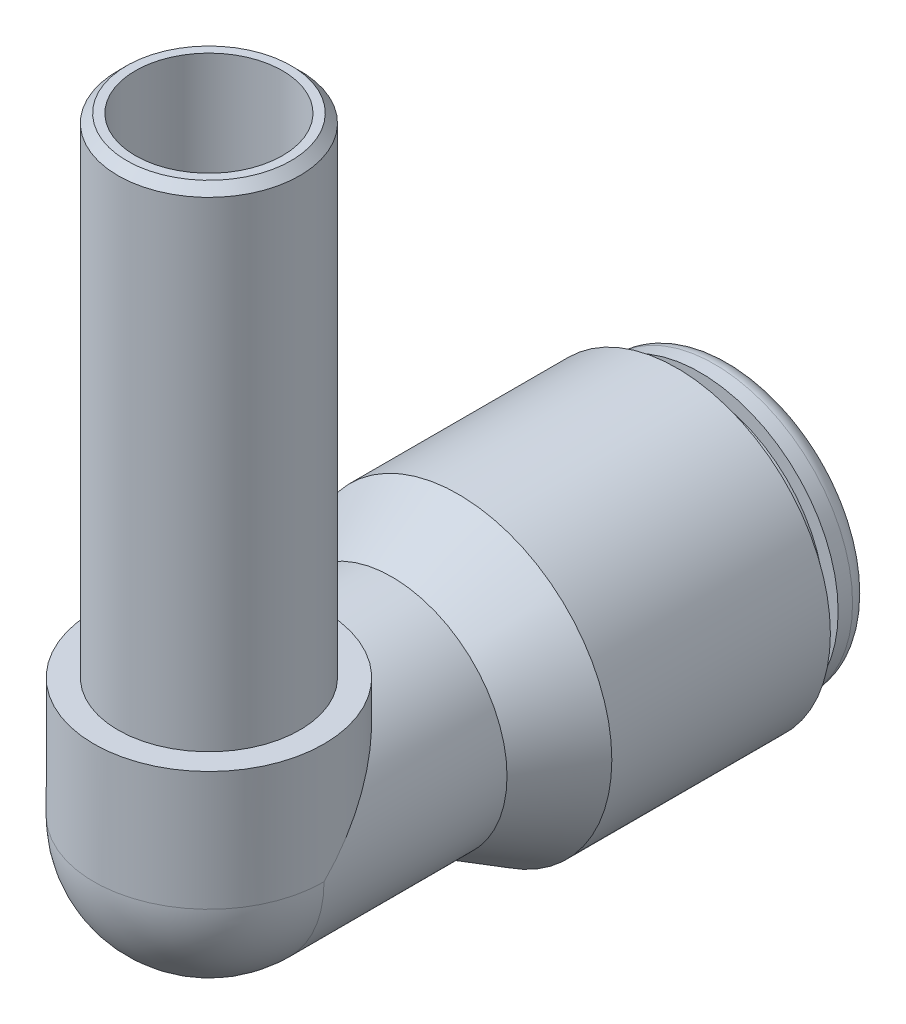
SolidWorks part; units mm, degrees
ref_plane "Front Plane" through (0, 0, 0) normal (0, 0, 1) x (1, 0, 0)
ref_plane "Top Plane" through (0, 0, 0) normal (0, 1, 0) x (1, 0, 0)
ref_plane "Right Plane" through (0, 0, 0) normal (1, 0, 0) x (0, 0, -1)
sketch "Sketch8" plane through (0, 0, 0) normal (1, 0, 0) x (0, 0, -1)
  line L0 (21.603, 6.075) -> (22.238, 6.075)
  line L1 (10.9728, 6.75) -> (20.587, 6.75)
  line L2 (0, 5.0625) -> (0, 4)
  line L3 (0, 4) -> (22.619, 4)
  line L4 (23, 5.313) -> (23, 4.381)
  line L5 (0, 6.75) -> (0, -16.25) construction
  line L6 (20.587, 6.75) -> (20.587, 5.4675)
  line L7 (20.587, 5.4675) -> (21.603, 5.4675)
  line L8 (21.603, 6.075) -> (21.603, 5.4675)
  line L9 (-6.75, -16.25) -> (6.75, -16.25) construction
  line L10 (0, 0) -> (23, 0) construction
  line L11 (23, -6.75) -> (0, -6.75) construction
  line L12 (22.619, 4) -> (23, 4.381)
  line L13 (0, 0) -> (0, 4) construction
  line L14 (0, 5.0625) -> (8.05, 5.0625)
  line L15 (8.05, 5.0625) -> (10.9728, 6.75)
  line L16 (0, -6.75) -> (0, 26.75) construction
  arc A0 (22.238, 6.075) -> (23, 5.313) centre (22.238, 5.313) cw
  point P1 (23, 4)
  point P20 (23, 6.075)
  point P24 (0, 5.25)
  point P26 (23, 6.75)
  point P27 (23, -6.75)
  point P28 (0, 8)
  dimension "D4" = 0.762
  dimension "tube od" = 8
  dimension "D1" = 1.397
  dimension "D2" = 1.016
  dimension "D3" = 10.935
  dimension "D6" = 12.15
  dimension "D9" = 30
  dimension "D10" = 10.125
  dimension "D5" = 14.95
  dimension "D8" = 13.5
revolve "Revolve1" add sketch "Sketch8" angle 360 about L10
sketch "Sketch10" plane through (0, 0, 0) normal (0, 0, 1) x (1, 0, 0)
  line L0 (0, 0) -> (8.5418, 0) construction
sketch "Sketch9" plane through (0, 0, 0) normal (0, 0, 1) x (1, 0, 0)
  circle A0 centre (0, 0) radius 4 construction
  circle A1 centre (0, 0) radius 4
  circle A2 centre (0, 0) radius 3.238
  dimension "D1" = 0.762
extrude "Extrude1" add sketch "Sketch9" against normal blind 5.0625
ref_axis "Axis1" through (8.5418, 0, 0) along (-1, 0, 0)
sketch "Sketch11" plane through (0, 0, 0) normal (0, 0, 1) x (1, 0, 0)
  line L0 (-5.0625, 0) -> (-3.238, 0)
  line L1 (-5.0625, 0) -> (-14.7876, 0) construction
  line L2 (3.238, 0) -> (5.0625, 0)
  arc A0 (-5.0625, 0) -> (5.0625, 0) centre (0, 0) ccw
  circle A1 centre (0, 0) radius 5.0625 construction
  arc A2 (-3.238, 0) -> (3.238, 0) centre (0, 0) ccw
  circle A3 centre (0, 0) radius 3.238 construction
revolve "Revolve2" add sketch "Sketch11" angle 90 about L1
sketch "Sketch14" plane through (0, 0, 0) normal (0, 1, 0) x (-1, 0, 0)
  line L2 (-5.0625, 0) -> (-3.238, 0)
  line L3 (-5.0625, 0) -> (-3.238, 0)
  line L4 (3.238, 0) -> (5.0625, 0)
  line L5 (3.238, 0) -> (5.0625, 0)
  arc A2 (5.0625, 0) -> (-5.0625, 0) centre (0, 0) ccw
  arc A3 (3.238, 0) -> (-3.238, 0) centre (0, 0) ccw
  arc A4 (5.0625, 0) -> (-5.0625, 0) centre (0, 0) ccw
  arc A5 (3.238, 0) -> (-3.238, 0) centre (0, 0) ccw
  dimension "D1" = 0
extrude "Extrude2" add sketch "Sketch14" along normal up to vertex (5.25 mm away) up to point (0, 5.25, 0)
sketch "Sketch16" plane through (0, 5.25, 0) normal (0, 1, 0) x (-1, 0, 0)
  circle A0 centre (0, 0) radius 5.0625
  arc A1 (5.0625, 0) -> (-5.0625, 0) centre (0, 0) ccw construction
  circle A2 centre (0, 0) radius 3.238
  arc A3 (3.238, 0) -> (-3.238, 0) centre (0, 0) ccw construction
extrude "Extrude5" add sketch "Sketch16" against normal up to vertex up to point (-5.0625, 0, 0)
sketch "Sketch12" plane through (0, 0, 0) normal (0, 1, 0) x (1, 0, 0)
  circle A0 centre (0, 0) radius 3.238
  circle A2 centre (0, 0) radius 3.238 construction
extrude "Cut-Extrude1" cut sketch "Sketch12" along normal through all
sketch "Sketch13" plane through (0, 0, -5.0625) normal (0, 0, 1) x (1, 0, 0)
  circle A0 centre (0, 0) radius 3.238
  circle A2 centre (0, 0) radius 3.238 construction
extrude "Cut-Extrude2" cut sketch "Sketch13" along normal up to vertex (5.0625 mm away) up to point (0, 0, 0)
ref_plane "Plane1" through (0, 26.75, 0) normal (0, 1, 0) x (-1, 0, 0)
sketch "Sketch15" plane through (0, 5.25, 0) normal (0, 1, 0) x (-1, 0, 0)
  circle A0 centre (0, 0) radius 3.238
  circle A1 centre (0, 0) radius 4
  circle A2 centre (0, 0) radius 3.238 construction
  dimension "stem od" = 8
extrude "Extrude4" add sketch "Sketch15" along normal up to surface (21.5 mm away) up to plane "Plane1"
chamfer "Chamfer1" distance 0.381 angle 45 1 edges at (0, 26.75, 4)
equation "\"D6@Sketch8\" = \"G@Sketch8\"*.9"
equation "\"D3@Sketch8\" = \"D6@Sketch8\"*.9"
equation "\"D10@Sketch8\" = \"G@Sketch8\"*.75"
equation "\"D5@Sketch8\" = \"L@Sketch8\"*.65"
equation "\"D1@Extrude1\" = \"D10@Sketch8\"/2"
equation "\"D8@Sketch8\" = \"G@Sketch8\""
